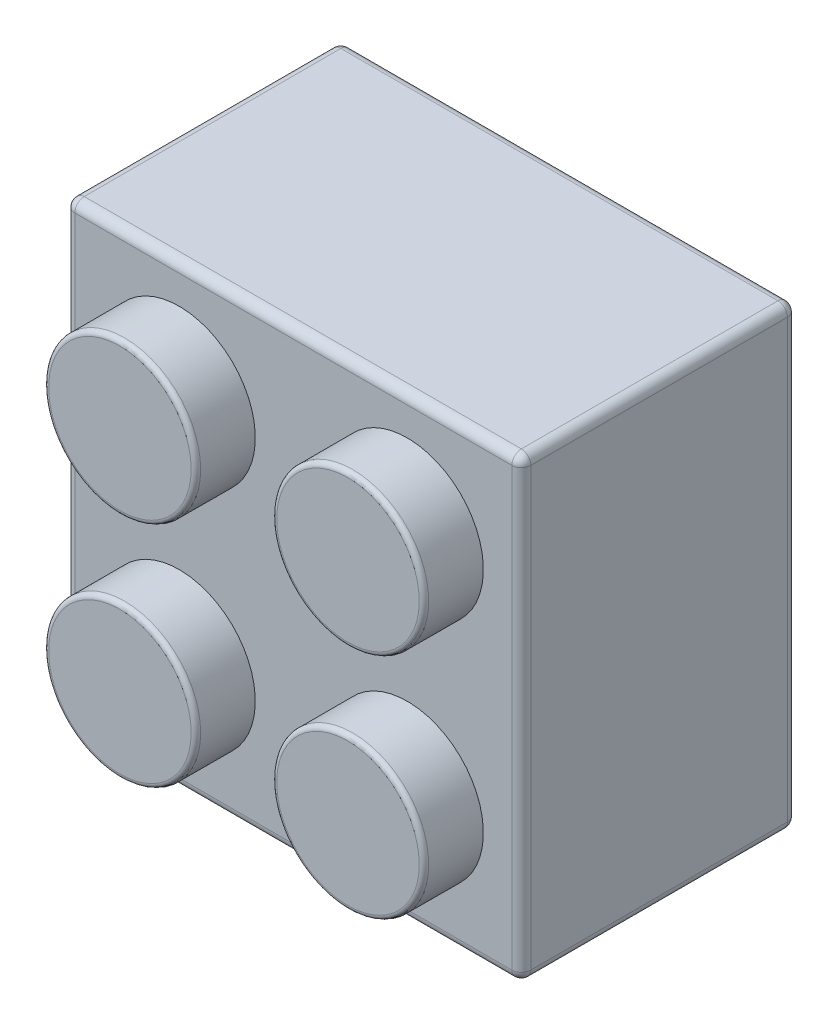
SolidWorks part; units mm, degrees
ref_plane "Plan de face" through (0, 0, 0) normal (0, 0, 1) x (1, 0, 0)
ref_plane "Plan de dessus" through (0, 0, 0) normal (0, 1, 0) x (1, 0, 0)
ref_plane "Plan de droite" through (0, 0, 0) normal (1, 0, 0) x (0, 0, -1)
sketch "Esquisse1" plane through (0, 0, 0) normal (0, 0, 1) x (1, 0, 0)
  line L0 (0, 59.0841) -> (0, -56.3445) construction
  line L1 (-61.915, 0) -> (66.2984, 0) construction
  line L2 (-48, 48) -> (48, 48)
  line L3 (48, 48) -> (48, -48)
  line L4 (48, -48) -> (-48, -48)
  line L5 (-48, -48) -> (-48, 48)
  line L6 (-40, 40) -> (40, 40)
  line L7 (40, 40) -> (40, -40)
  line L8 (40, -40) -> (-40, -40)
  line L9 (-40, -40) -> (-40, 40)
  point P9 (0, -56.3445)
  point P10 (0, 0)
  point P11 (0, 0)
  point P12 (0, 0)
  point P13 (0, 0)
  point P14 (0, 0)
  point P15 (0, 0)
  point P16 (0, 0)
  point P17 (0, 59.0841)
  point P18 (0, 0)
  point P19 (-61.915, 0)
  point P20 (0, 0)
  point P21 (66.2984, 0)
  dimension "D1" = 96
  dimension "D2" = 8
extrude "Boss.-Extru.1" add sketch "Esquisse1" along normal blind 48
sketch "Esquisse2" plane through (0, 0, 48) normal (0, 0, 1) x (1, 0, 0)
  line L1 (-48, 48) -> (48, 48)
  line L2 (-48, 48) -> (-48, -48)
  line L3 (-48, -48) -> (48, -48)
  line L4 (48, 48) -> (48, -48)
extrude "Boss.-Extru.3" add sketch "Esquisse2" along normal offset from surface (10 mm away) 58 up to face at (0, 0, 0)
sketch "Esquisse3" plane through (0, 0, 58) normal (0, 0, 1) x (1, 0, 0)
  line L0 (-48, -48) -> (48, 48) construction
  line L1 (48, -48) -> (-48, 48) construction
  line L2 (-24, 40) -> (24, 40) construction
  line L3 (-48, 48) -> (48, 48) construction
  circle A0 centre (-24, 24) radius 16
  circle A1 centre (24, 24) radius 16
  circle A2 centre (24, -24) radius 16
  circle A3 centre (-24, -24) radius 16
  point P19 (0, 0)
  point P21 (0, 0)
  dimension "D1" = 32
  dimension "D3" = 8
  dimension "D2" = 4
extrude "Boss.-Extru.4" add sketch "Esquisse3" along normal blind 12.5
sketch "Esquisse4" plane through (0, 0, 0) normal (0, 0, -1) x (-1, 0, 0)
  circle A0 centre (0, 0) radius 18.5
  circle A1 centre (0, 0) radius 11.5
  point P4 (0, 0)
  dimension "D1" = 37
  dimension "D2" = 23
extrude "Boss.-Extru.5" add sketch "Esquisse4" against normal up to surface (48 mm away) up to face at (0, 0, 48)
chamfer "Chanfrein1" distance 48 angle 5 1 edges at (18.5, 0, 48) first distance on face at (-18.5, 0, 0)
fillet "Congé1" radius 2 1 edges at (-48, 0, 0)
fillet "Congé2" radius 2 3 edges at (-48, -48, 30) (-47.4142, -48, 0.5858) (1, -48, 0)
fillet "Congé3" radius 2 3 edges at (48, -48, 30) (48, -47.4142, 0.5858) (48, 1, 0)
fillet "Congé4" radius 2 16 edges at (-48, 1, 58) (-47.4142, -47.4142, 58) (0, -48, 58) (47.4142, -47.4142, 58) (48, 48, 30) (47.4142, 48, 0.5858) (-48, 48, 30) (-47.4142, 48, 0.5858) (0, 48, 58) (48, 1, 58) (0, -40, 0) (40, 0, 0) (0, 40, 0) (-40, 0, 48) (-40, 0, 0) (0, 48, 0)
fillet "Congé5" radius 1 4 edges at (40, -24, 70.5) (-8, -24, 70.5) (-8, 24, 70.5) (40, 24, 70.5)
fillet "Congé6" radius 1 2 edges at (-11.5, 0, 0) (-18.5, 0, 0)
